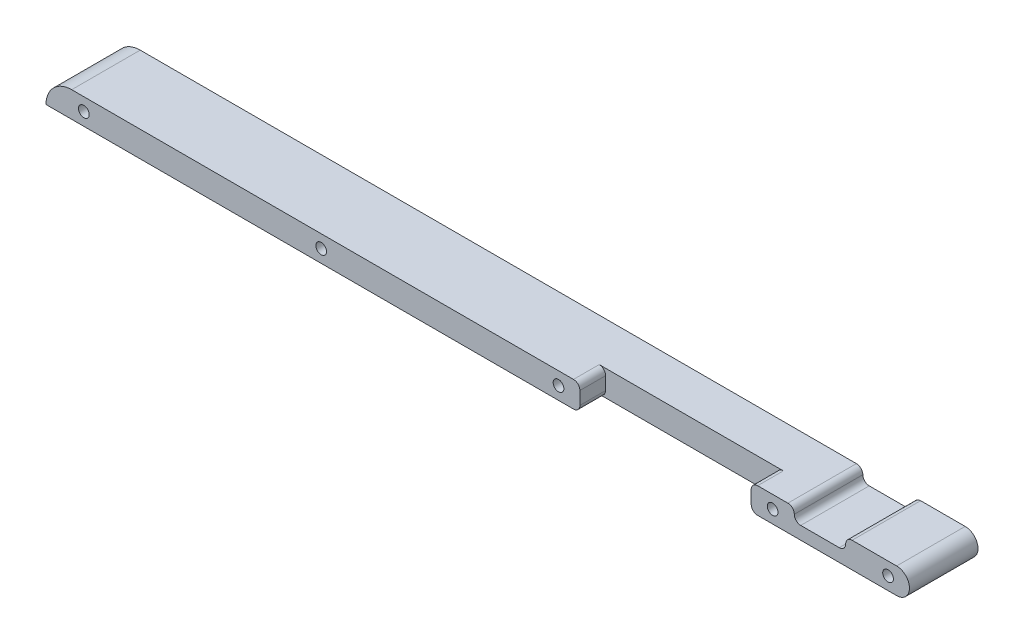
SolidWorks part; units mm, degrees
material "POM Ацеталь кополимер"
ref_plane "Спереди" through (0, 0, 0) normal (0, 0, 1) x (1, 0, 0)
ref_plane "Сверху" through (0, 0, 0) normal (0, 1, 0) x (1, 0, 0)
ref_plane "Справа" through (0, 0, 0) normal (1, 0, 0) x (0, 0, -1)
sketch "Model" plane through (0, 0, 0) normal (0, 0, 1) x (1, 0, 0)
  line L0 (100.82, 3) -> (3, 3)
  line L1 (0, 0) -> (100.82, 0)
  line L21 (100.82, 3) -> (100.82, 0)
  arc A15 (3, 3) -> (0, 0) centre (3, 0) ccw
  dimension "D1" = 3
  dimension "D2" = 100.82
  dimension "D3" = 3
extrude "База" add sketch "Model" along normal blind 8
sketch "Эскиз2" plane through (0, 0, 8) normal (0, 0, 1) x (1, 0, 0)
  line L0 (100.82, 3) -> (3, 3) construction
  line L5 (0, 0) -> (100.82, 0) construction
  line L7 (62.34, 3) -> (82.34, 3)
  line L8 (62.34, 3) -> (62.34, 0)
  line L9 (62.34, 0) -> (82.34, 0)
  line L10 (82.34, 3) -> (82.34, 0)
  point P16 (72.34, 0)
  dimension "D1" = 20
  dimension "D3" = 72.34
extrude "Вырез шестерни" cut sketch "Эскиз2" against normal blind 3
hole_wizard "Резьба М1.6" positions "Эскиз3" profile "Эскиз4" tap size "M1.6" standard "DIN" end condition through all
sketch "Эскиз3" plane through (0, 0, 8) normal (0, 0, 1) x (1, 0, 0)
  line L0 (4.42, 1.5) -> (4.42, 3) construction
  line L1 (62.34, 3) -> (3, 3) construction
  line L4 (4.42, 1.5) -> (4.42, 0) construction
  line L5 (0, 0) -> (62.34, 0) construction
  line L9 (82.34, 0) -> (82.34, 3) construction
  line L18 (98.32, 1.5) -> (100.82, 1.5) construction
  line L19 (100.82, 0) -> (100.82, 3) construction
  line L20 (62.34, 3) -> (62.34, 0) construction
  line L21 (4.42, 1.5) -> (32.13, 1.5) construction
  line L22 (32.13, 1.5) -> (59.84, 1.5) construction
  point P0 (4.42, 1.5)
  point P19 (59.84, 1.5)
  point P25 (84.84, 1.5)
  point P44 (98.32, 1.5)
  point P57 (100.82, 1.5)
  point P62 (32.13, 1.5)
  dimension "D1" = 2.5
  dimension "D2" = 4.42
  dimension "D3" = 2.5
  dimension "D4" = 2.5
sketch "Эскиз4" plane through (4.42, 1.5, 8) normal (1, 0, 0) x (0, -1, 0)
  line L0 (0, 0) -> (0, 8)
  line L1 (0, 8) -> (0.625, 8)
  line L2 (0.625, 8) -> (0.625, 0)
  line L5 (0.625, 0) -> (0, 0)
  line L11 (0, -6.35) -> (0, 107.95) construction
  dimension "Диаметр проходного сверла" = 1.25
  dimension "Глубина проходного сверла" = 8
cosmetic thread "Отверстие резьбы1" parameters "D2"=1.6
cosmetic thread "Отверстие резьбы2" parameters "D2"=1.6
cosmetic thread "Отверстие резьбы3" parameters "D2"=1.6
cosmetic thread "Отверстие резьбы4" parameters "D2"=1.6
cosmetic thread "Отверстие резьбы5" parameters "D2"=1.6
sketch "Эскиз7" plane through (0, 0, 8) normal (0, 0, 1) x (1, 0, 0)
  line L5 (100.82, 3) -> (82.34, 3) construction
  line L6 (87.37, 3) -> (93.37, 3)
  line L7 (87.37, 3) -> (87.37, 1.5)
  line L8 (87.37, 1.5) -> (93.37, 1.5)
  line L9 (93.37, 3) -> (93.37, 1.5)
  line L10 (100.82, 0) -> (100.82, 3) construction
  point P2 (100.82, 1.5)
  point P13 (90.37, 1.5)
  dimension "D1" = 90.37
  dimension "D2" = 6
extrude "Вырез крепления двигателя" cut sketch "Эскиз7" against normal through all
fillet "Скругление2" 2 edges at (100.82, 3, 4) (100.82, 0, 4) type full round first side face at (97.095, 3, 4) second side face at (61.375, 0, 5.25) middle face at (100.82, 1.5, 4)
fillet "Скругление3" radius 0.75 8 edges at (62.34, 0, 6.5) (82.34, 0, 6.5) (93.37, 1.5, 4) (93.37, 3, 4) (87.37, 1.5, 4) (87.37, 3, 4) (82.34, 3, 6.5) (62.34, 3, 6.5)
